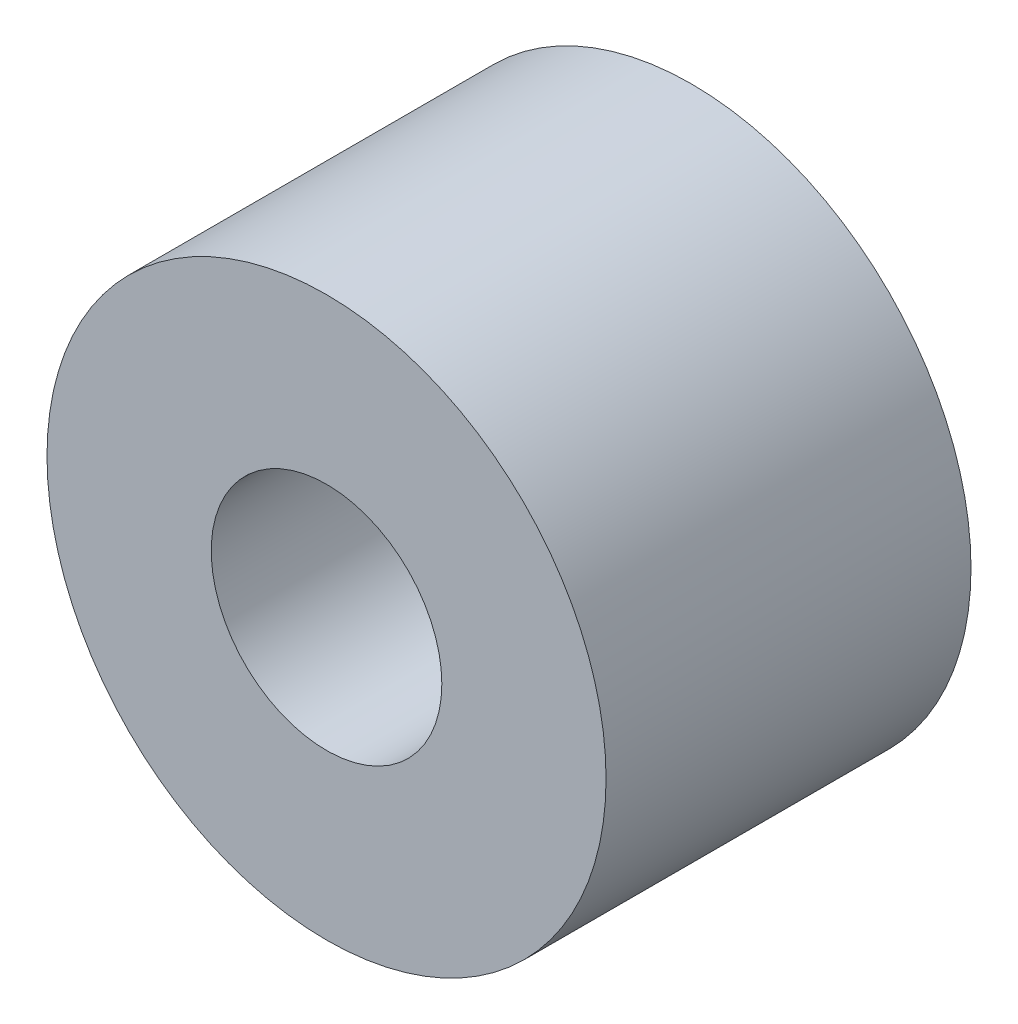
SolidWorks part; units mm, degrees
ref_plane "Front Plane" through (0, 0, 0) normal (0, 0, 1) x (1, 0, 0)
ref_plane "Top Plane" through (0, 0, 0) normal (0, 1, 0) x (1, 0, 0)
ref_plane "Right Plane" through (0, 0, 0) normal (1, 0, 0) x (0, 0, -1)
sketch "Sketch1" plane through (0, 0, 0) normal (0, 0, 1) x (1, 0, 0)
  circle A0 centre (0, 0) radius 2.25
  circle A1 centre (0, 0) radius 1.65
  dimension "D1" = 4.5
  dimension "D2" = 3.3
extrude "Boss-Extrude1" add sketch "Sketch1" along normal blind 1
sketch "Sketch2" plane through (0, 0, 1) normal (0, 0, 1) x (1, 0, 0)
  circle A0 centre (0, 0) radius 4
  circle A1 centre (0, 0) radius 1.65
  circle A2 centre (0, 0) radius 1.65 construction
  dimension "D1" = 8
extrude "Boss-Extrude2" add sketch "Sketch2" along normal blind 5
chamfer "Chamfer1" distance 1 distance2 2.25 1 edges at (2.25, 0, 1) first distance on face at (2.25, 0, 1)
